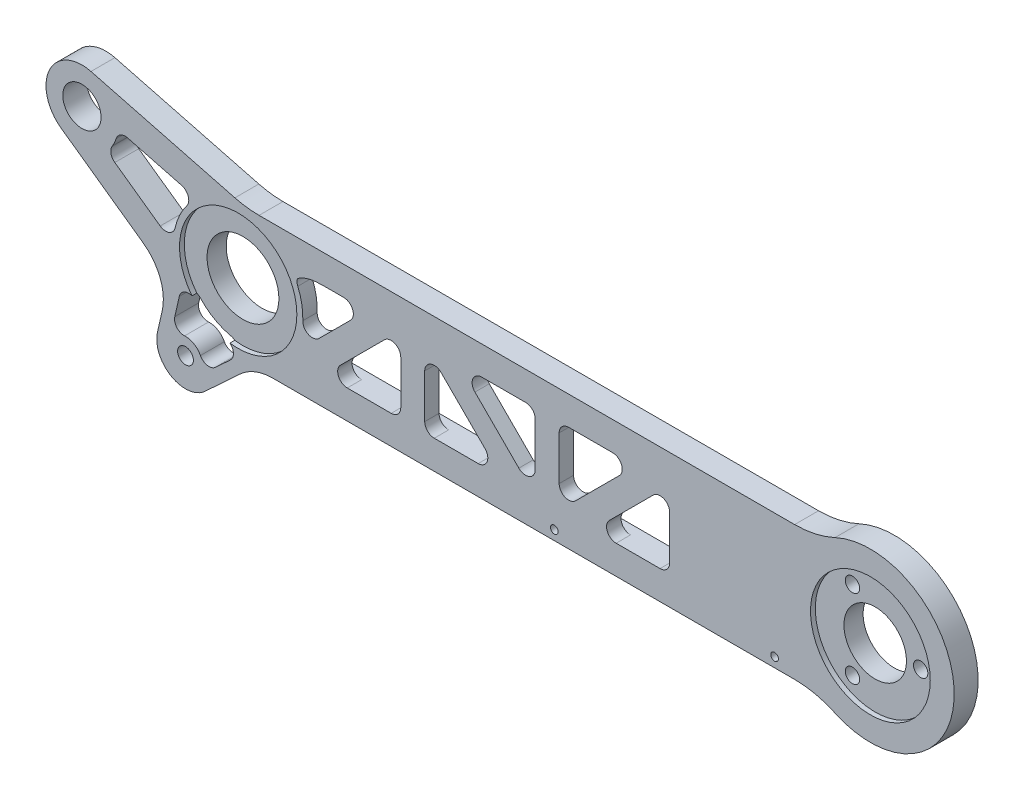
SolidWorks part; units mm, degrees
material "6061 合金"
ref_plane "前视基准面" through (0, 0, 0) normal (0, 0, 1) x (1, 0, 0)
ref_plane "上视基准面" through (0, 0, 0) normal (0, 1, 0) x (1, 0, 0)
ref_plane "右视基准面" through (0, 0, 0) normal (1, 0, 0) x (0, 0, -1)
other "Configuration Table"
sketch "草图1" plane through (0, 0, 0) normal (0, 0, 1) x (1, 0, 0)
  line L0 (0, 0) -> (132, 0)
  line L1 (0, 0) -> (-32.6271, 15.2143)
  line L2 (-30.7368, 22.4721) -> (-0.6858, 14.6456)
  line L3 (-36.9719, 9.101) -> (-8.1104, -11.4115)
  line L4 (4.3549, 14) -> (116.1807, 14)
  line L5 (0, -14) -> (116.1807, -14)
  arc A0 (-30.7368, 22.4721) -> (-36.9719, 9.101) centre (-32.6271, 15.2143) ccw
  arc A1 (-8.1104, -11.4115) -> (0, -14) centre (0, 0) ccw
  arc A2 (124.6177, -15.8667) -> (124.6177, 15.8667) centre (132, 0) ccw
  arc A3 (116.1807, -14) -> (124.6177, -15.8667) centre (116.1807, -34) cw
  arc A4 (116.1807, 14) -> (124.6177, 15.8667) centre (116.1807, 34) ccw
  arc A5 (4.3549, 14) -> (-0.6858, 14.6456) centre (4.3549, 34) cw
  dimension "D4" = 15
  dimension "D5" = 28
  dimension "D6" = 35
  dimension "D7" = 20
  dimension "D1" = 132
  dimension "D2" = 36
  dimension "D3" = 155
extrude "凸台-拉伸1" add sketch "草图1" along normal blind 5 contours L4 A5 L2 A0 L3 A1 L5 A3 A2 A4 region at (59.3478, 1.19, 0)
sketch "草图2" plane through (0, 0, 5) normal (0, 0, 1) x (1, 0, 0)
  circle A0 centre (-32.6271, 15.2143) radius 4
  dimension "D1" = 8
extrude "切除-拉伸1" cut sketch "草图2" against normal blind 5
sketch "草图3" plane through (0, 0, 5) normal (0, 0, 1) x (1, 0, 0)
  circle A0 centre (0, 0) radius 7.5
  dimension "D1" = 15
extrude "切除-拉伸2" cut sketch "草图3" against normal blind 10
sketch "草图4" plane through (0, 0, 5) normal (0, 0, 1) x (1, 0, 0)
  line L8 (116.1807, 8) -> (4.3549, 8)
  line L9 (-2.198, 8.8393) -> (-32.249, 16.6658)
  line L10 (-33.496, 13.9916) -> (-4.6345, -6.5209)
  line L11 (0, -8) -> (116.1807, -8)
  line L12 (116.1807, 8) -> (4.3549, 8)
  line L13 (-2.198, 8.8393) -> (-32.249, 16.6658)
  line L14 (-33.496, 13.9916) -> (-4.6345, -6.5209)
  line L15 (0, -8) -> (116.1807, -8)
  circle A6 centre (0, 0) radius 13.5
  circle A7 centre (-32.6271, 15.2143) radius 7.5
  circle A8 centre (0, 0) radius 7.5 construction
  arc A12 (-2.198, 8.8393) -> (4.3549, 8) centre (4.3549, 34) ccw
  arc A13 (-32.249, 16.6658) -> (-33.496, 13.9916) centre (-32.6271, 15.2143) ccw
  arc A14 (-4.6345, -6.5209) -> (0, -8) centre (0, 0) ccw
  arc A15 (127.1488, -10.4267) -> (116.1807, -8) centre (116.1807, -34) ccw
  arc A16 (127.1488, -10.4267) -> (127.1488, 10.4267) centre (132, 0) ccw
  arc A17 (116.1807, 8) -> (127.1488, 10.4267) centre (116.1807, 34) ccw
  arc A18 (-2.198, 8.8393) -> (4.3549, 8) centre (4.3549, 34) ccw
  arc A19 (-32.249, 16.6658) -> (-33.496, 13.9916) centre (-32.6271, 15.2143) ccw
  arc A20 (-4.6345, -6.5209) -> (0, -8) centre (0, 0) ccw
  arc A21 (127.1488, -10.4267) -> (116.1807, -8) centre (116.1807, -34) ccw
  arc A22 (127.1488, -10.4267) -> (127.1488, 10.4267) centre (132, 0) ccw
  arc A23 (116.1807, 8) -> (127.1488, 10.4267) centre (116.1807, 34) ccw
  dimension "D2" = 6
  dimension "D1" = 6
extrude "切除-拉伸3" cut sketch "草图4" against normal blind 10 contours A7 L14 A6 L13 region at (-18.1289, 8.4536, 5)
sketch "草图5" plane through (0, 0, 5) normal (0, 0, 1) x (1, 0, 0)
  line L4 (10.8743, -8) -> (26.8743, 8)
  line L5 (33.9453, 8) -> (17.9453, -8)
  line L6 (33.9453, 8) -> (33.9453, -8)
  line L7 (38.9453, 8) -> (38.9453, -8)
  line L8 (116.1807, 8) -> (4.3549, 8)
  line L9 (-2.198, 8.8393) -> (-32.249, 16.6658)
  line L10 (-33.496, 13.9916) -> (-4.6345, -6.5209)
  line L11 (0, -8) -> (116.1807, -8)
  line L12 (116.1807, 8) -> (4.3549, 8)
  line L13 (-2.198, 8.8393) -> (-32.249, 16.6658)
  line L14 (-33.496, 13.9916) -> (-4.6345, -6.5209)
  line L15 (0, -8) -> (116.1807, -8)
  line L16 (38.9453, 8) -> (54.9453, -8)
  line L17 (46.0164, 8) -> (62.0164, -8)
  line L18 (62.0164, -8) -> (62.0164, 8)
  line L19 (67.0164, 8) -> (67.0164, -8)
  line L20 (67.0164, -8) -> (83.0164, 8)
  line L21 (74.0875, -8) -> (90.0875, 8)
  line L22 (90.0875, 8) -> (90.0875, -8)
  line L23 (95.0875, 8) -> (95.0875, -8)
  circle A6 centre (0, 0) radius 13.5
  arc A12 (-2.198, 8.8393) -> (4.3549, 8) centre (4.3549, 34) ccw
  arc A13 (-32.249, 16.6658) -> (-33.496, 13.9916) centre (-32.6271, 15.2143) ccw
  arc A14 (-4.6345, -6.5209) -> (0, -8) centre (0, 0) ccw
  arc A15 (127.1488, -10.4267) -> (116.1807, -8) centre (116.1807, -34) ccw
  arc A16 (127.1488, -10.4267) -> (127.1488, 10.4267) centre (132, 0) ccw
  arc A17 (116.1807, 8) -> (127.1488, 10.4267) centre (116.1807, 34) ccw
  arc A18 (-2.198, 8.8393) -> (4.3549, 8) centre (4.3549, 34) ccw
  arc A19 (-32.249, 16.6658) -> (-33.496, 13.9916) centre (-32.6271, 15.2143) ccw
  arc A20 (-4.6345, -6.5209) -> (0, -8) centre (0, 0) ccw
  arc A21 (127.1488, -10.4267) -> (116.1807, -8) centre (116.1807, -34) ccw
  arc A22 (127.1488, -10.4267) -> (127.1488, 10.4267) centre (132, 0) ccw
  arc A23 (116.1807, 8) -> (127.1488, 10.4267) centre (116.1807, 34) ccw
  dimension "D2" = 45
  dimension "D3" = 5
  dimension "D4" = 5
  dimension "D5" = 5
  dimension "D6" = 5
  dimension "D7" = 45
  dimension "D8" = 5
  dimension "D9" = 5
  dimension "D1" = 6
extrude "切除-拉伸4" cut sketch "草图5" against normal blind 10 contours L5 L15 L6 | A6 L4 L12 | L16 L7 L15 | L17 L18 L12 | L19 L20 L12 | L22 L21 L15 region at (17.4374, 3.434, 5) region at (28.612, -2.6667, 5) region at (44.2787, -2.6667, 5) region at (56.6831, 2.6667, 5) region at (72.3498, 2.6667, 5) region at (84.7542, -2.6667, 5)
fillet "圆角1" radius 2 22 edges at (54.9453, -8, 2.5) (38.9453, -8, 2.5) (38.9453, 8, 2.5) (90.0875, -8, 2.5) (74.0875, -8, 2.5) (90.0875, 8, 2.5) (33.9453, -8, 2.5) (17.9453, -8, 2.5) (33.9453, 8, 2.5) (-25.1378, 14.8138, 2.5) (-8.507, 10.4824, 2.5) (-27.5063, 9.7345, 2.5) (10.8743, 8, 2.5) (26.8743, 8, 2.5) (10.8743, -8, 2.5) (62.0164, 8, 2.5) (62.0164, -8, 2.5) (46.0164, 8, 2.5) (83.0164, 8, 2.5) (67.0164, -8, 2.5) (67.0164, 8, 2.5) (-13.4982, -0.2213, 2.5)
sketch "草图6" plane through (0, 0, 5) normal (0, 0, 1) x (1, 0, 0)
  circle A0 centre (132, 0) radius 6.525
  dimension "D1" = 13.05
extrude "切除-拉伸5" cut sketch "草图6" against normal blind 10
sketch "草图7" plane through (0, 0, 5) normal (0, 0, 1) x (1, 0, 0)
  line L0 (132, 0) -> (94, 0) construction
  circle A0 centre (94, 0) radius 1.65
  dimension "D1" = 3.3
  dimension "D2" = 38
extrude "切除-拉伸6" [suppressed] cut sketch "草图7" against normal blind 12
sketch "草图8" plane through (0, 0, 5) normal (0, 0, 1) x (1, 0, 0)
  circle A0 centre (132, 0) radius 9.5 construction
  circle A1 centre (141.5, 0) radius 1.5
  circle A2 centre (127.25, -8.2272) radius 1.5
  circle A3 centre (127.25, 8.2272) radius 1.5
  dimension "D1" = 19
  dimension "D2" = 3
extrude "切除-拉伸7" cut sketch "草图8" against normal blind 10
sketch "草图9" plane through (0, 0, 5) normal (0, 0, 1) x (1, 0, 0)
  point P0 (132, 0)
sketch "草图11" plane through (0, 0, 5) normal (0, 0, 1) x (1, 0, 0)
  line L1 (0, -14) -> (116.1807, -14) construction
  circle A0 centre (66, -12) radius 0.8
  circle A1 centre (112, -12) radius 0.8
  circle A3 centre (132, 0) radius 6.525 construction
  dimension "D1" = 46
  dimension "D2" = 1.6
  dimension "D3" = 1.6
  dimension "D4" = 20
  dimension "D6" = 2
extrude "切除-拉伸8" cut sketch "草图11" against normal blind 10
sketch "草图12" plane through (0, 0, 0) normal (0, 0, 1) x (1, 0, 0)
  circle A0 centre (132, 0) radius 6.55
  circle A1 centre (132, 0) radius 6.025
  dimension "D1" = 12.05
  dimension "D2" = 13.1
sketch "草图13" plane through (0, 0, 0) normal (0, 0, -1) x (-1, 0, 0)
  line L0 (0, 0) -> (16.0711, -27.836) construction
  line L1 (12.1886, 2.7726) -> (16.8505, -17.7217) construction
  line L2 (-8.4954, -9.1694) -> (6.9222, -23.4539) construction
  line L3 (13.8522, -4.5406) -> (-8.1014, -9.5344)
  line L4 (-8.1014, -9.5344) -> (6.9222, -23.4539)
  line L5 (13.8522, -4.5406) -> (16.8505, -17.7217)
  line L6 (0, -14) -> (-116.1807, -14) construction
  circle A0 centre (-132, 0) radius 47.75 construction
  circle A1 centre (0, 0) radius 30 construction
  circle A2 centre (11, -19.0526) radius 8 construction
  circle A3 centre (11, -19.0526) radius 1.65
  circle A4 centre (0, 0) radius 12.5 construction
  arc A5 (6.9222, -23.4539) -> (16.8505, -17.7217) centre (11, -19.0526) ccw
  circle A6 centre (0, 0) radius 7.5 construction
  dimension "D1" = 95.5
  dimension "D2" = 60
  dimension "D3" = 16
  dimension "D4" = 3.3
  dimension "D5" = 25
  dimension "D6" = 6
  dimension "D7" = 60
extrude "凸台-拉伸3" add sketch "草图13" against normal up to surface (5 mm away) up to face at (66.8, -12, 5)
fillet "圆角3" radius 10 2 edges at (3.2816, -14, 2.5) (-14.3985, -6.9424, 2.5)
sketch "草图15" plane through (0, 0, 0) normal (0, 0, -1) x (-1, 0, 0)
  line L0 (1.6315, -15.1439) -> (4.7397, -18.0237)
  line L4 (-0.4057, -16.6645) -> (6.9222, -23.4539) construction
  line L5 (12.2993, -8.9849) -> (13.2391, -13.1165)
  line L6 (16.8505, -17.7217) -> (15.8782, -13.447) construction
  circle A4 centre (0, 0) radius 10 construction
  arc A5 (11.1839, -15.5574) -> (7.8812, -17.4642) centre (11, -19.0526) ccw
  arc A6 (2.5635, -11.723) -> (8.8707, -8.0816) centre (0, 0) ccw
  arc A7 (4.7397, -18.0237) -> (7.8812, -17.4642) centre (6.099, -16.5566) ccw
  arc A8 (11.1839, -15.5574) -> (13.2391, -13.1165) centre (11.2889, -13.5602) ccw
  arc A9 (12.2993, -8.9849) -> (8.8707, -8.0816) centre (10.3491, -9.4285) ccw
  arc A10 (1.6315, -15.1439) -> (2.5635, -11.723) centre (2.9908, -13.6768) cw
  dimension "D3" = 2
  dimension "D1" = 20
  dimension "D2" = 24
extrude "切除-拉伸9" cut sketch "草图15" against normal blind 5
sketch "草图16" plane through (0, 0, 0) normal (0, 0, -1) x (-1, 0, 0)
  line L0 (-4.3549, 14) -> (-116.1807, 14) construction
  line L1 (-4.3549, 14) -> (-116.1807, 14)
  line L2 (-7.2021, -14) -> (-116.1807, -14) construction
  line L3 (-7.2021, -14) -> (-116.1807, -14)
  line L4 (-4.3549, 8) -> (-116.1807, 8)
  line L5 (-60.2678, 14) -> (-60.2678, -21.3508) construction
  line L6 (-108.2678, 14) -> (-108.2678, -21.3508)
  line L7 (-7.2021, -8) -> (-116.1807, -8)
  line L8 (-10.2678, 14) -> (-10.2678, -21.3508)
  dimension "D1" = 6
  dimension "D2" = 6
  dimension "D3" = 48
  dimension "D4" = 50
extrude "切除-拉伸10" cut sketch "草图16" against normal blind 2 contours L5 L4 L6 L7 | L4 L5 L7 L8 region at (35.2678, 0, 0) region at (84.2678, 0, 0)
fillet "圆角4" radius 8 4 edges at (108.2678, 8, 1) (108.2678, -8, 1) (10.2678, -8, 1) (10.2678, 8, 1) curvature continuous yes
sketch "草图17" plane through (0, 0, 5) normal (0, 0, 1) x (1, 0, 0)
  circle A0 centre (132, 0) radius 12.5
  circle A1 centre (0, 0) radius 12.25
  dimension "D1" = 25
  dimension "D2" = 24.5
extrude "切除-拉伸11" cut sketch "草图17" against normal blind 1
